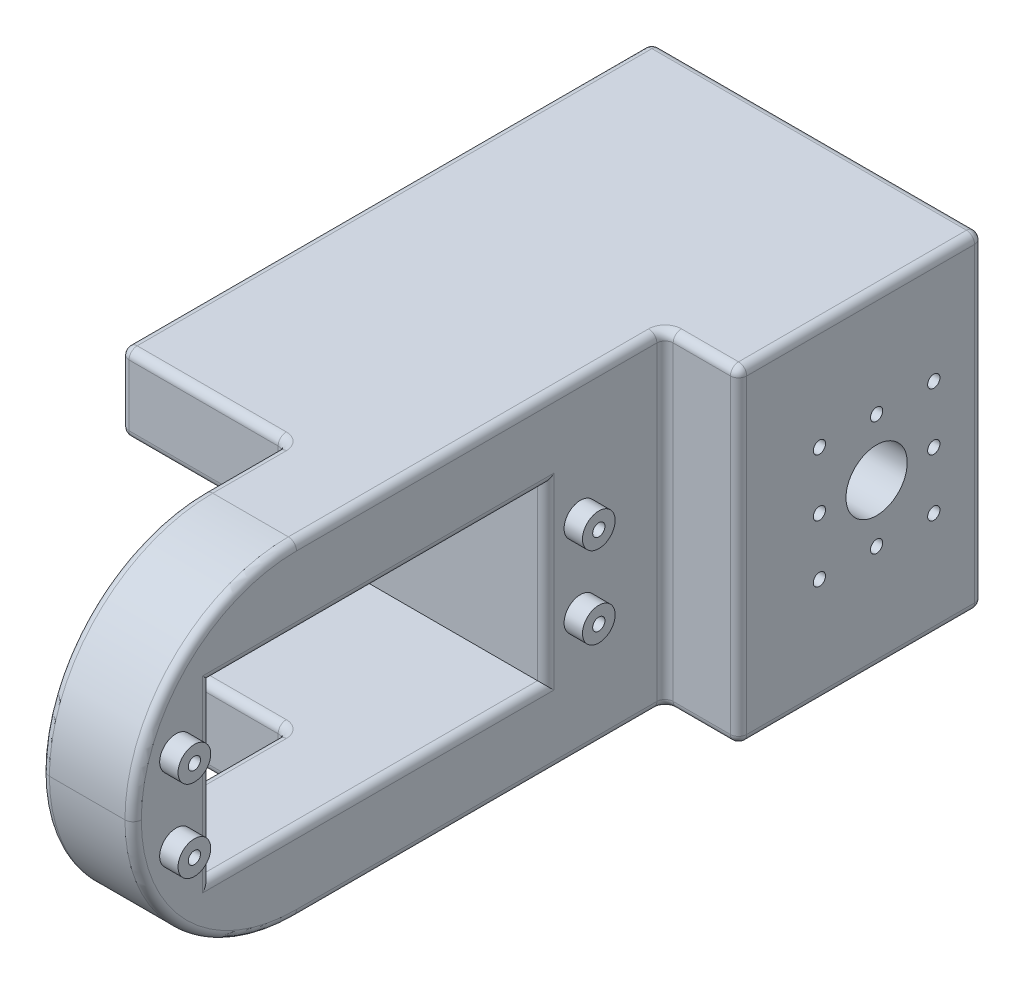
SolidWorks part; units mm, degrees
material "ABS"
ref_plane "Front Plane" through (0, 0, 0) normal (0, 0, 1) x (1, 0, 0)
ref_plane "Top Plane" through (0, 0, 0) normal (0, 1, 0) x (1, 0, 0)
ref_plane "Right Plane" through (0, 0, 0) normal (1, 0, 0) x (0, 0, -1)
sketch "Sketch4" plane through (0, 0, 0) normal (0, 1, 0) x (1, 0, 0)
  line L17 (-25.25, 20) -> (-5, 20)
  line L20 (-5, 20) -> (15.25, 20)
  line L21 (-25.25, -75) -> (-5, -75)
  line L22 (-5, -75) -> (15.25, -75)
  line L23 (15.25, 20) -> (15.25, -75)
  line L24 (-25.25, 20) -> (-25.25, -75)
extrude "MBODY" add sketch "Sketch4" along normal blind 40 contours L17 L20 L23 L22 L21 L24
sketch "Sketch5" plane through (0, 0, -20) normal (0, 0, -1) x (-1, 0, 0)
  line L3 (0, 20) -> (0, 15)
  line L4 (0, 20) -> (0, 25)
  line L5 (0, 25) -> (10, 25)
  line L6 (10, 25) -> (10, 35)
  line L7 (10, 35) -> (0, 35)
  line L8 (0, 15) -> (10, 15)
  line L9 (10, 15) -> (10, 5)
  line L10 (10, 5) -> (0, 5)
  circle A1 centre (0, 5) radius 0.75
  circle A2 centre (10, 5) radius 0.75
  circle A3 centre (10, 15) radius 0.75
  circle A4 centre (0, 15) radius 0.75
  circle A5 centre (0, 25) radius 0.75
  circle A6 centre (10, 25) radius 0.75
  circle A7 centre (10, 35) radius 0.75
  circle A8 centre (0, 35) radius 0.75
extrude "FrontScrews" cut sketch "Sketch5" against normal blind 3 contours A8 | A7 | A6 | A5 | A4 | A3 | A1 | A2
sketch "Sketch7" plane through (0, 0, -20) normal (0, 0, -1) x (-1, 0, 0)
  circle A0 centre (5, 20) radius 2.75
extrude "GUIDKNOB" add sketch "Sketch7" along normal blind 4 contours A0
sketch "Sketch10" plane through (15.25, 0, 0) normal (1, 0, 0) x (0, 0, -1)
  line L1 (-65.5, 20) -> (-65.5, 30.5)
  line L2 (-65.5, 20) -> (-65.5, 9.5)
  line L3 (-65.5, 30.5) -> (-24.5, 30.5)
  line L4 (-65.5, 9.5) -> (-24.5, 9.5)
  line L5 (-24.5, 9.5) -> (-24.5, 30.5)
  point P0 (-45, 30.5)
extrude "ServoCut" cut sketch "Sketch10" against normal blind 40.5 contours L4 L5 L3 L1 L2
fillet "RoundEdge" radius 20 2 edges at (-5, 0, 75) (-5, 40, 75)
sketch "Sketch23" plane through (15.25, 0, 0) normal (1, 0, 0) x (0, 0, -1)
  line L0 (-9.8948, 0) -> (-79.8948, 0)
  line L2 (-9.8948, 40) -> (-9.8948, 0)
  line L4 (-9.8948, 40) -> (-79.8948, 40)
  line L5 (-79.8948, 40) -> (-79.8948, 0)
extrude "TOPPUSHDOWN" cut sketch "Sketch23" against normal blind 9
sketch "Sketch12" plane through (6.25, 0, 0) normal (1, 0, 0) x (0, 0, -1)
  line L0 (-69.75, 15) -> (-65, 15)
  line L1 (-65, 25) -> (-69.75, 25)
  line L2 (-69.75, 25) -> (-69.75, 15)
  line L3 (-20.25, 15) -> (-20.25, 25)
  line L6 (-25, 25) -> (-20.25, 25)
  circle A0 centre (-69.75, 25) radius 2
  circle A1 centre (-69.75, 15) radius 2
  circle A2 centre (-20.25, 15) radius 2
  circle A3 centre (-20.25, 25) radius 2
extrude "SERVOHOLDERS" add sketch "Sketch12" along normal blind 2.25 contours A3 | A2 | A0 | A1
sketch "Sketch24" plane through (8.5, 0, 0) normal (1, 0, 0) x (0, 0, -1)
  circle A0 centre (-69.75, 25) radius 0.75
  circle A1 centre (-69.75, 15) radius 0.75
  circle A2 centre (-20.25, 25) radius 0.75
  circle A3 centre (-20.25, 15) radius 0.75
extrude "SERVOHOLDERSCREWS" cut sketch "Sketch24" against normal blind 3.25
sketch "Sketch14" plane through (-25.25, 0, 0) normal (-1, 0, 0) x (0, 0, 1)
  line L4 (75, 40) -> (75, 0)
  line L8 (75, 40) -> (45, 40)
  line L9 (75, 0) -> (45, 0)
  line L10 (45, 40) -> (45, 0)
extrude "CABLEACCESS" cut sketch "Sketch14" against normal blind 20.25 contours L8 L10 L9 L4
fillet "ROUNDEDGES" radius 1 38 edges at (-5, 0, 50) (-5, 40, 50) (-5, 9.5, 55.25) (-5, 30.5, 55.25) (-5, 20, 65.5) (-5, 5.8579, 69.1421) (-5, 34.1421, 69.1421) (15.25, 40, -5.0526) (15.25, 0, -5.0526) (15.25, 20, -20) (-5, 40, -20) (-5, 0, -20) (-25.25, 20, -20) (-25.25, 40, 12.5) (-25.25, 30.5, 34.75) (-25.25, 20, 24.5) (-25.25, 9.5, 34.75) (-25.25, 0, 12.5) (-5, 4.75, 45) (-5, 35.25, 45) (-25.25, 35.25, 45) (-25.25, 4.75, 45) (-15.125, 9.5, 45) (-15.125, 40, 45) (-15.125, 30.5, 45) (-15.125, 0, 45) (6.25, 9.5, 45) (6.25, 20, 65.5) (6.25, 30.5, 45) (6.25, 20, 24.5) (6.25, 0, 32.4474) (6.25, 5.8579, 69.1421) (6.25, 34.1421, 69.1421) (6.25, 40, 32.4474) (10.75, 40, 9.8948) (6.25, 20, 9.8948) (10.75, 0, 9.8948) (15.25, 20, 9.8948)
sketch "Sketch8" plane through (15.25, 50, 0) normal (-1, 0, 0) x (0, 0, -1)
  line L0 (14, 37) -> (14, 30)
  line L2 (14, 37) -> (7, 37)
  line L3 (7, 37) -> (0, 37)
  line L4 (0, 37) -> (0, 30)
  line L6 (14, 23) -> (7, 23)
  line L7 (7, 23) -> (0, 23)
  line L8 (0, 23) -> (0, 30)
  line L11 (14, 30) -> (14, 23)
  circle A0 centre (0, 37) radius 0.75
  circle A1 centre (7, 37) radius 0.75
  circle A2 centre (14, 37) radius 0.75
  circle A4 centre (14, 23) radius 0.75
  circle A5 centre (7, 23) radius 0.75
  circle A6 centre (0, 23) radius 0.75
  circle A7 centre (0, 30) radius 0.75
  circle A8 centre (14, 30) radius 0.75
extrude "SideScrews1" cut sketch "Sketch8" along normal blind 3 contours A4 | A2 | A1 | A0 | A7 | A6 | A5 | A8
sketch "Sketch17" plane through (-25.25, 15, 0) normal (1, 0, 0) x (0, -1, 0)
  line L1 (-12, 7) -> (-12, 14)
  line L2 (-12, 14) -> (-5, 14)
  line L3 (-5, 14) -> (2, 14)
  line L4 (2, 14) -> (2, 7)
  line L5 (2, 7) -> (2, -0.0049)
  line L6 (2, -0.0049) -> (-5, -0.0049)
  line L7 (-5, -0.0049) -> (-12, -0.0049)
  line L8 (-12, -0.0049) -> (-12, 7)
  circle A0 centre (-12, 14) radius 0.75
  circle A1 centre (-5, 14) radius 0.75
  circle A2 centre (2, 14) radius 0.75
  circle A3 centre (2, 7) radius 0.75
  circle A4 centre (-12, 7) radius 0.75
  circle A5 centre (-12, -0.0049) radius 0.75
  circle A6 centre (-5, -0.0049) radius 0.75
  circle A7 centre (2, -0.0049) radius 0.75
extrude "SideScrews2" cut sketch "Sketch17" along normal blind 3 contours A7 | A3 | A2 | A1 | A0 | A4 | A5 | A6
sketch "Sketch18" plane through (-25.25, 25, 0) normal (1, 0, 0) x (0, 1, 0)
  circle A0 centre (-5, -7) radius 3.75
extrude "SIDEGUIDEHOLE" cut sketch "Sketch18" along normal blind 40.5 contours A0
